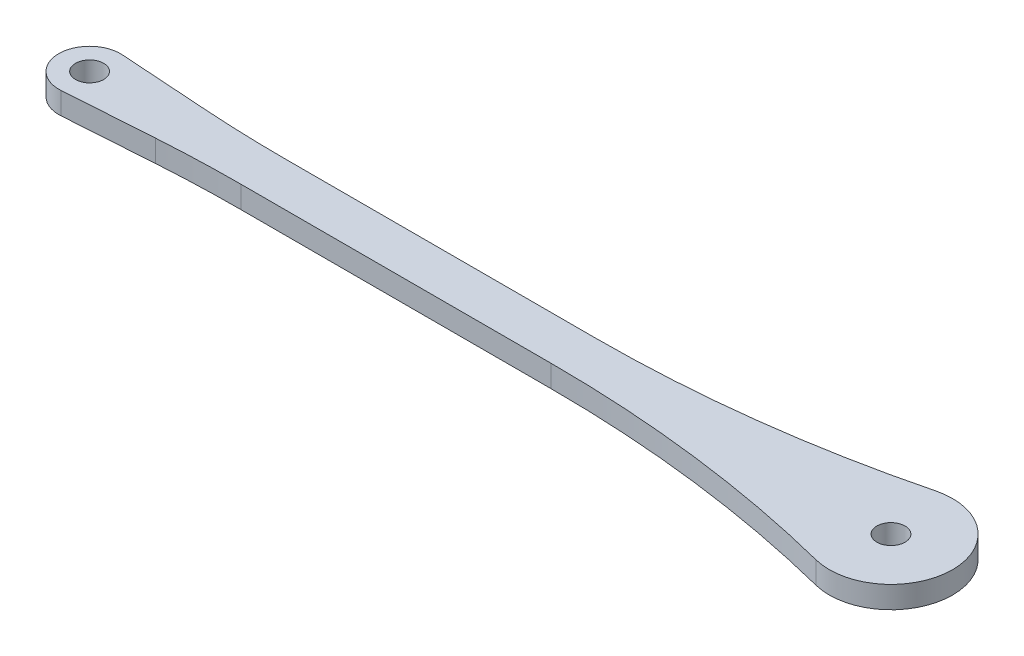
SolidWorks part; units mm, degrees
ref_plane "Front Plane" through (0, 0, 0) normal (0, 0, 1) x (1, 0, 0)
ref_plane "Top Plane" through (0, 0, 0) normal (0, 1, 0) x (1, 0, 0)
ref_plane "Right Plane" through (0, 0, 0) normal (1, 0, 0) x (0, 0, -1)
sketch "Sketch1" plane through (0, 0, 0) normal (0, 1, 0) x (1, 0, 0)
  line L0 (-57.487, 4.435) -> (-38.735, 3.175)
  line L1 (57.785, 3.175) -> (-57.785, 3.175)
  line L2 (57.785, 3.175) -> (57.785, -3.175)
  line L3 (57.785, -3.175) -> (-57.785, -3.175)
  line L4 (-57.785, 3.175) -> (-57.785, -3.175)
  line L5 (57.785, 3.175) -> (-57.785, -3.175) construction
  line L6 (57.785, -3.175) -> (-57.785, 3.175) construction
  line L7 (-38.735, -3.175) -> (-57.487, -4.435)
  line L9 (55.0459, 8.4575) -> (38.735, 3.175)
  line L10 (38.735, -3.175) -> (55.0459, -8.4575)
  circle A1 centre (57.785, 0) radius 3.175
  circle A2 centre (57.785, 0) radius 2.032
  circle A4 centre (-57.785, 0) radius 3.175
  circle A5 centre (-57.785, 0) radius 2.032
  circle A6 centre (-57.785, 0) radius 4.445
  circle A7 centre (57.785, 0) radius 8.89
  point P0 (0, 0)
  dimension "D3" = 4.064
  dimension "D4" = 8.89
  dimension "D7" = 17.78
  dimension "D1" = 6.35
  dimension "D2" = 115.57
  dimension "D5" = 19.05
  dimension "D6" = 19.05
  dimension "D8" = 19.05
  dimension "D9" = 19.05
extrude "Boss-Extrude1" add sketch "Sketch1" along normal blind 3.175 contours A4 L3 A1 L1 | A5 L4 A4 | A5 L4 A4 | A2 L2 A1 | A2 L2 A1 | L3 A6 L1 A4 | A6 L3 A4 L1 | A6 L1 L0 | A6 L7 L3 | A7 L9 L1 | A7 L1 A1 L3 | L1 A7 L3 A1 | A7 L3 L10
fillet "Fillet2" radius 177.8 4 edges at (-38.735, 1.5875, 3.175) (38.735, 1.5875, 3.175) (38.735, 1.5875, -3.175) (-38.735, 1.5875, -3.175)
fillet "Fillet3" [suppressed] radius 254
